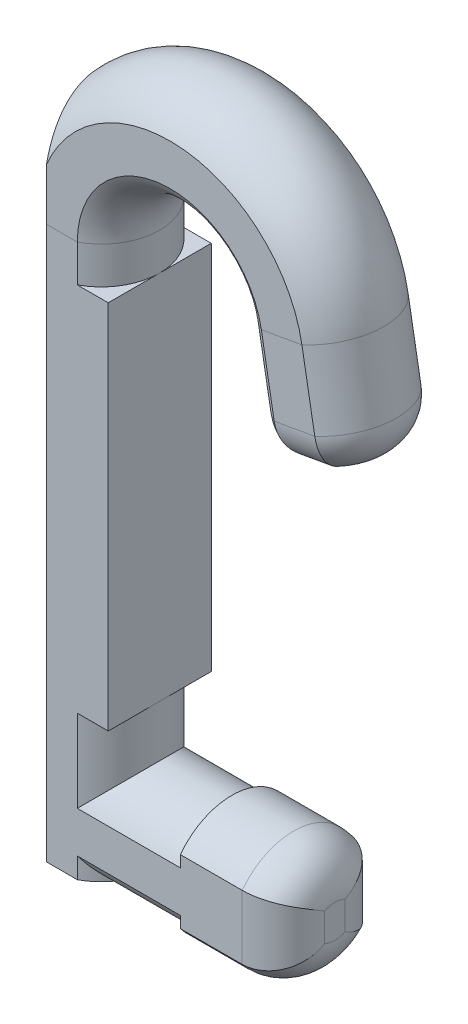
SolidWorks part; units mm, degrees
ref_plane "前视基准面" through (0, 0, 0) normal (0, 0, 1) x (1, 0, 0)
ref_plane "上视基准面" through (0, 0, 0) normal (0, 1, 0) x (1, 0, 0)
ref_plane "右视基准面" through (0, 0, 0) normal (1, 0, 0) x (0, 0, -1)
other "Configuration Table"
sketch "草图1" plane through (0, 0, 0) normal (0, 0, 1) x (1, 0, 0)
  line L0 (0, 0) -> (0, 24.8)
  line L1 (10.9164, 25.7551) -> (11.8862, 20.2551)
  line L2 (0, 0) -> (0, -2)
  arc A0 (0, 24.8) -> (10.9164, 25.7551) centre (5.5, 24.8) cw
  dimension "D1" = 5.5
  dimension "D2" = 10
  dimension "D3" = 24.8
  dimension "6" = 5.5
ref_plane "基准面3" through (0, -2, 0) normal (0, 1, 0) x (1, 0, 0)
sketch "草图13" plane through (0, -2, 0) normal (0, 1, 0) x (1, 0, 0)
  line L1 (-1, -2.5) -> (1, -2.5)
  line L3 (-1, 2.5) -> (1, 2.5)
  line L5 (-1, -2.5) -> (1, 2.5) construction
  line L6 (-1, 2.5) -> (1, -2.5) construction
  line L7 (0, 2.5) -> (0, -2.5) construction
  line L8 (1, 2.5) -> (1, -2.5) construction
  arc A0 (1, 2.5) -> (1, -2.5) centre (-0.3333, 0) cw
  arc A1 (-1, 2.5) -> (-1, -2.5) centre (0.3333, 0) ccw
  point P11 (1, 0)
  point P12 (2.5, 0)
  point P21 (0, 0)
  dimension "D2" = 2
  dimension "D1" = 5
  dimension "D3" = 1.5
sweep "扫描2" add profiles "草图13" path "草图1"
sketch "草图15" plane through (0, 0, 0) normal (0, 0, 1) x (1, 0, 0)
  line L0 (10.9164, 25.7551) -> (11.8862, 20.2551) construction
  line L1 (0, 0) -> (0, 24.8) construction
  line L3 (10.9164, 25.7551) -> (11.8862, 20.2551) construction
  line L4 (0, 0) -> (0, 24.8) construction
  line L5 (0, 0) -> (11, 0)
  arc A0 (10.9164, 25.7551) -> (0, 24.8) centre (5.5, 24.8) ccw construction
  arc A2 (10.9164, 25.7551) -> (0, 24.8) centre (5.5, 24.8) ccw construction
  dimension "D1" = 11
ref_plane "基准面2" through (11, 0, 0) normal (1, 0, 0) x (0, 0, -1)
sketch "草图16" plane through (11, 0, 0) normal (1, 0, 0) x (0, 0, -1)
  line L2 (-2.5, 0) -> (2.5, 0) construction
  line L4 (-2.5, -1) -> (-2.5, 1)
  line L6 (2.5, -1) -> (2.5, 1)
  line L7 (-2.5, -1) -> (2.5, 1) construction
  line L8 (-2.5, 1) -> (2.5, -1) construction
  line L9 (-2.5, -1) -> (2.5, -1) construction
  arc A3 (-2.5, -1) -> (2.5, -1) centre (0, 0.3333) ccw
  arc A4 (-2.5, 1) -> (2.5, 1) centre (0, -0.3333) cw
  point P0 (0, 0)
  point P9 (0, -2.5)
  dimension "D1" = 2
  dimension "D2" = 1.5
  dimension "D3" = 5
sweep "扫描4" add profiles "草图16" path "草图15"
sketch "草图17" plane through (11, 0, 0) normal (1, 0, 0) x (0, 0, -1)
  line L0 (-2.5, 1) -> (-2.5, -1) construction
  line L1 (-2.5, 1.5555) -> (-2.5, -1.5555)
  line L2 (2.5, -1) -> (2.5, 1) construction
  line L3 (2.5, -1) -> (2.5, 1) construction
  line L6 (2.5, 1.5555) -> (2.5, -1.5555)
  line L7 (2.5, 24.8) -> (2.5, 0) construction
  line L10 (-2.8, 1.073) -> (-2.8, -1.073)
  line L11 (2.8, -1.073) -> (2.8, 1.073)
  line L12 (-2.5, 0) -> (2.5, 0) construction
  arc A0 (2.5, -1.5555) -> (-2.5, -1.5555) centre (0, 0.3333) cw
  arc A15 (2.8, 1.073) -> (-2.8, 1.073) centre (0, -0.3333) ccw
  arc A16 (-2.8, -1.073) -> (2.8, -1.073) centre (0, 0.3333) ccw
  arc A17 (2.5, 1.5555) -> (-2.5, 1.5555) centre (0, -0.3333) ccw
  dimension "D1" = 0.3
extrude "凸台-拉伸1" add sketch "草图17" against normal blind 5
ref_plane "基准面4" through (1, 0, 0) normal (1, 0, 0) x (0, 0, -1)
sketch "草图19" plane through (1, 0, 0) normal (1, 0, 0) x (0, 0, -1)
  line L1 (-2.5, 5) -> (2.5, 5)
  line L2 (2.5, 0) -> (2.5, 24.8)
  line L3 (-2.5, 24.8) -> (-2.5, 0)
  line L4 (2.5, 5) -> (2.5, 23)
  line L5 (-2.5, 23) -> (-2.5, 5)
  line L6 (-2.5, 23) -> (2.5, 23)
  line L7 (0, 0) -> (0, 23) construction
  line L11 (2.5, 24.8) -> (-2.5, 24.8)
  line L12 (-2.5, 0) -> (2.5, 0)
  dimension "D2" = 18
  dimension "D3" = 5
  dimension "D1" = 0
extrude "凸台-拉伸2" add sketch "草图19" along normal blind 1.5
fillet "圆角2" radius 2 8 edges at (11.8862, 20.2551, 2.5) (14.3483, 20.6892, 0) (11.8862, 20.2551, -2.5) (9.4242, 19.8209, 0) (11, -2.8, 0) (11, 0, 2.5) (11, 2.8, 0) (11, 0, -2.5)
ref_plane "基准面5" through (-0.5, 0, 0) normal (1, 0, 0) x (0, 0, -1)
sketch "草图20" plane through (-0.5, 0, 0) normal (1, 0, 0) x (0, 0, -1)
  line L1 (4, -4) -> (-4, -4)
  line L2 (4, -4) -> (4, 36)
  line L3 (4, 36) -> (-4, 36)
  line L4 (-4, -4) -> (-4, 36)
  point P6 (-4.968, -3.5996)
  dimension "D1" = 4
  dimension "D2" = 4
  dimension "D3" = 4
  dimension "D4" = 40
extrude "切除-拉伸1" cut sketch "草图20" against normal through all
